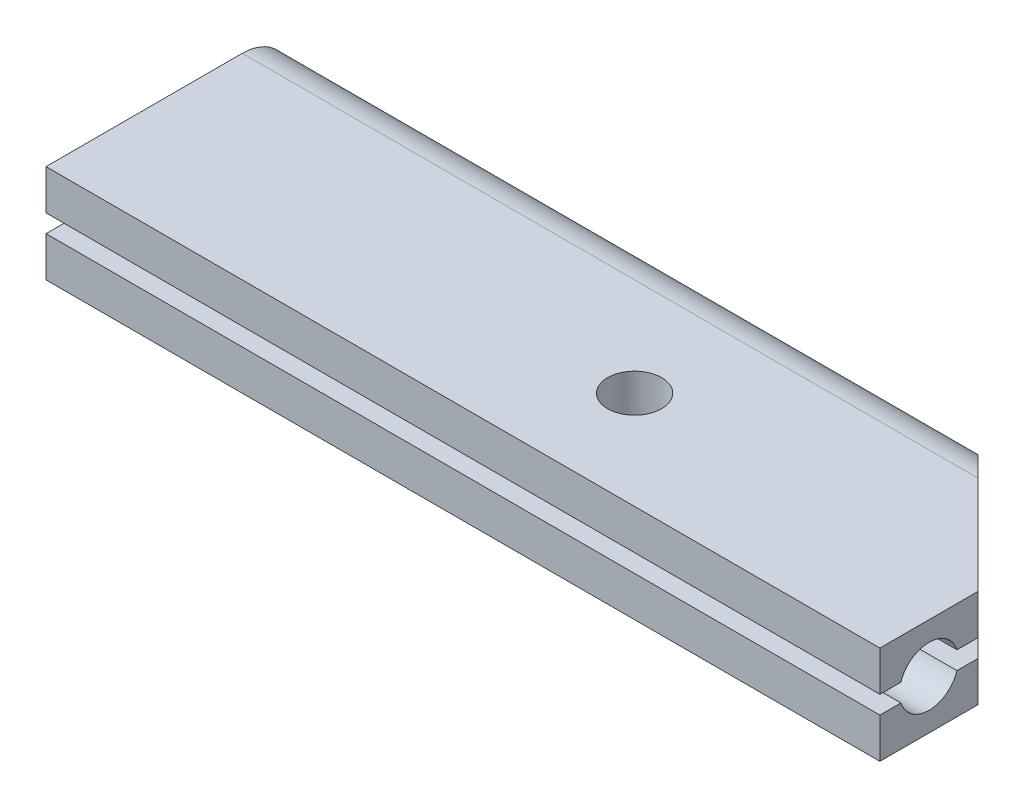
SolidWorks part; units mm, degrees
ref_plane "前视基准面" through (0, 0, 0) normal (0, 0, 1) x (1, 0, 0)
ref_plane "上视基准面" through (0, 0, 0) normal (0, 1, 0) x (1, 0, 0)
ref_plane "右视基准面" through (0, 0, 0) normal (1, 0, 0) x (0, 0, -1)
sketch "草图1" plane through (0, 0, 0) normal (0, 1, 0) x (1, 0, 0)
  line L0 (14, 5) -> (17, 2)
  line L1 (0, 0) -> (17, 0)
  line L2 (0, 0) -> (0, 5)
  line L3 (0, 5) -> (17, 5)
  line L4 (17, 0) -> (17, 5)
  dimension "D1" = 5
  dimension "D2" = 2
  dimension "D3" = 45
  dimension "D4" = 17
extrude "凸台-拉伸1" add sketch "草图1" along normal blind 2 contours L1 L4 L0 L3 L2 region at (8.0807, 0, -2.4161)
sketch "草图2" plane through (17, 0, 0) normal (1, 0, 0) x (0, 0, -1)
  line L0 (0, 2) -> (0, 0) construction
  circle A0 centre (1, 1) radius 0.6
  point P4 (0, 0)
  dimension "D1" = 1
  dimension "1.2" = 1.2
extrude "切除-拉伸1" cut sketch "草图2" against normal through all
fillet "圆角1" radius 1 2 edges at (7, 0, -5) (7, 2, -5)
sketch "草图3" plane through (0, 0, 0) normal (-1, 0, 0) x (0, 0, 1)
  line L0 (0, 2) -> (0, 0) construction
  line L1 (4, 0.8164) -> (-4, 0.8164)
  line L2 (4, 0.8164) -> (4, 1.1836)
  line L3 (4, 1.1836) -> (-4, 1.1836)
  line L4 (-4, 0.8164) -> (-4, 1.1836)
  line L5 (4, 0.8164) -> (-4, 1.1836) construction
  line L6 (4, 1.1836) -> (-4, 0.8164) construction
  point P0 (0, 1)
  dimension "D1" = 8
  dimension "0.2" = 0.3672
extrude "切除-拉伸2" cut sketch "草图3" against normal through all
sketch "草图4" plane through (0, 2, 0) normal (0, 1, 0) x (1, 0, 0)
  line L0 (17, 0) -> (17, 2) construction
  line L2 (0, 0) -> (17, 0) construction
  circle A0 centre (10, 2) radius 0.55
  point P6 (11.328, 0)
  dimension "1.1" = 1.1
  dimension "D1" = 7
  dimension "D2" = 2
extrude "切除-拉伸3" cut sketch "草图4" against normal through all
